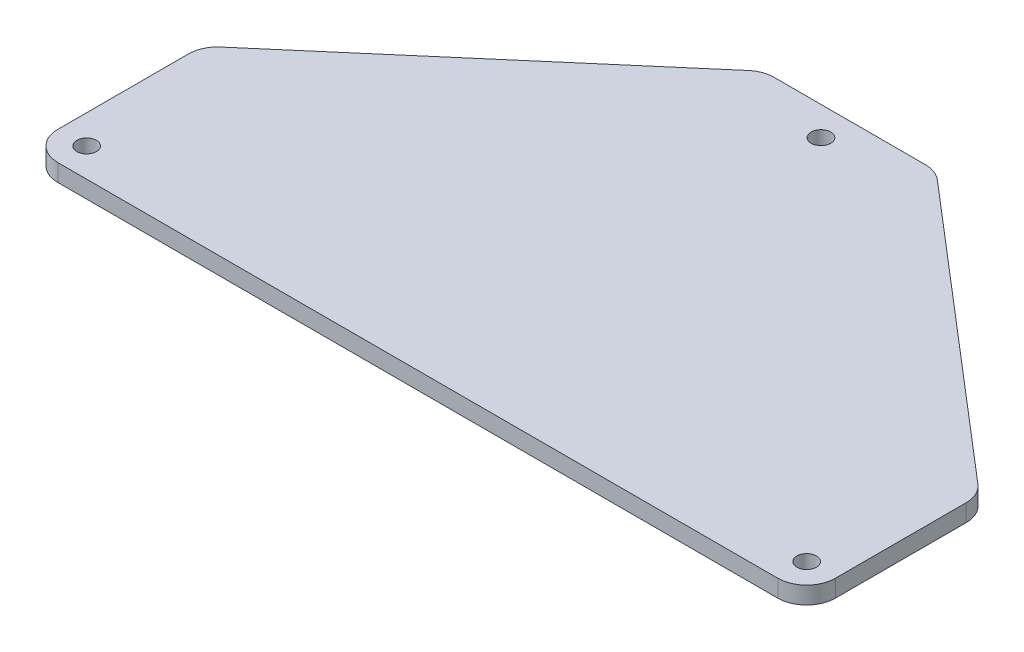
SolidWorks part; units mm, degrees
ref_plane "Front" through (0, 0, 0) normal (0, 0, 1) x (1, 0, 0)
ref_plane "Top" through (0, 0, 0) normal (0, 1, 0) x (1, 0, 0)
ref_plane "Right" through (0, 0, 0) normal (1, 0, 0) x (0, 0, -1)
sketch "Esquisse1" plane through (0, 0, 0) normal (0, 1, 0) x (1, 0, 0)
  line L0 (-67.5, 0) -> (67.5, 0)
  line L1 (0, 0) -> (67.5, 0) construction
  line L2 (0, 0) -> (0, 75) construction
  line L3 (0, 75) -> (67.5, 75) construction
  line L4 (67.5, 0) -> (67.5, 75) construction
  line L5 (67.5, 0) -> (67.5, 30)
  line L6 (67.5, 30) -> (15, 75)
  line L7 (15, 75) -> (-15, 75)
  line L8 (-67.5, 30) -> (-15, 75)
  line L9 (-67.5, 0) -> (-67.5, 30)
  dimension "D1" = 67.5
  dimension "D2" = 30
  dimension "D3" = 15
  dimension "D4" = 75
extrude "Boss.-Extru.1" add sketch "Esquisse1" along normal blind 3
fillet "Congé1" radius 5 6 edges at (-67.5, 1.5, 0) (-67.5, 1.5, -30) (-15, 1.5, -75) (15, 1.5, -75) (67.5, 1.5, -30) (67.5, 1.5, 0)
sketch "Esquisse2" plane through (0, 3, 0) normal (0, 1, 0) x (1, 0, 0)
  line L0 (-62.5, 0) -> (62.5, 0) construction
  line L1 (67.5, 5) -> (67.5, 27.7003) construction
  circle A0 centre (-62.5, 5) radius 1
  circle A1 centre (62.5, 5) radius 1
  circle A2 centre (0, 70) radius 1
  dimension "D4" = 2
  dimension "D5" = 2
  dimension "D6" = 2
  dimension "D1" = 62.5
  dimension "D2" = 62.5
  dimension "D3" = 65
  dimension "D7" = 5
  dimension "D8" = 5
  dimension "D9" = 67.5
extrude "Enlèv. mat.-Extru.2" cut sketch "Esquisse2" against normal up to surface (3 mm away) up to face at (0, 0, -35.4067)
hole_wizard "Dégagement M31" positions "Esquisse3" profile "Esquisse4" hole size "M3" standard "ISO"
sketch "Esquisse3" plane through (0, 3, 0) normal (0, 1, 0) x (1, 0, 0)
  point P0 (-62.5, 5)
  point P3 (62.5, 5)
  point P6 (0, 70)
sketch "Esquisse4" plane through (-62.5, 3, -5) normal (1, 0, 0) x (0, 0, 1)
  line L0 (0, 0) -> (0, 11.0215)
  line L1 (0, 11.0215) -> (1.7, 10)
  line L2 (1.7, 10) -> (1.7, 0)
  line L5 (1.7, 0) -> (0, 0)
  line L10 (0, 11.0215) -> (-1.7, 10) construction
  line L11 (0, -6.35) -> (0, 107.95) construction
  dimension "Diamètre du perçage" = 3.4
  dimension "Profondeur du perçage" = 10
  dimension "Angle de pointe" = 118
equation "\"D1@Esquisse1\"=135/2"
equation "\"D1@Esquisse2\"=125/2"
